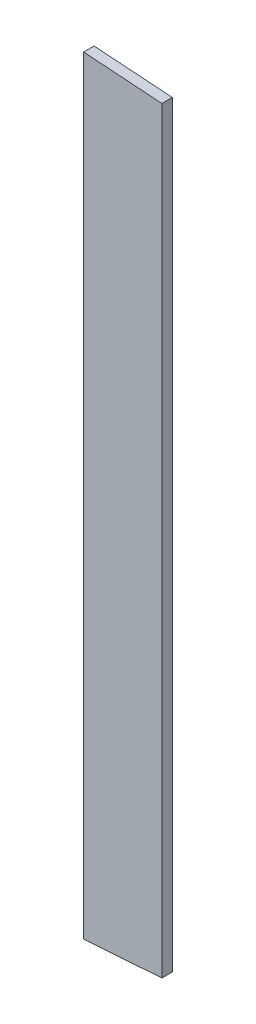
SolidWorks part; units mm, degrees
ref_plane "Front Plane" through (0, 0, 0) normal (0, 0, 1) x (1, 0, 0)
ref_plane "Top Plane" through (0, 0, 0) normal (0, 1, 0) x (1, 0, 0)
ref_plane "Right Plane" through (0, 0, 0) normal (1, 0, 0) x (0, 0, -1)
sketch "Sketch1" plane through (0, 0, 2463.85) normal (0, 0, 1) x (1, 0, 0)
  line L0 (-49.7697, 346.1083) -> (-64.7697, 345.0594)
  line L1 (-140.9262, 339.734) -> (58.5866, 353.6853) construction
  line L2 (-64.7697, 345.0594) -> (-64.7697, 492.4158)
  line L3 (58.5866, 483.7899) -> (-140.9262, 497.7412) construction
  line L4 (-64.7697, 492.4158) -> (-49.7697, 491.3669)
  line L5 (-49.7697, 491.3669) -> (-49.7697, 346.1083)
  dimension "D1" = 15
extrude "Boss-Extrude1" add sketch "Sketch1" along normal blind 2
ref_plane "Plane1" through (-57.2697, 0, 0) normal (1, 0, 0) x (0, 0, -1)
